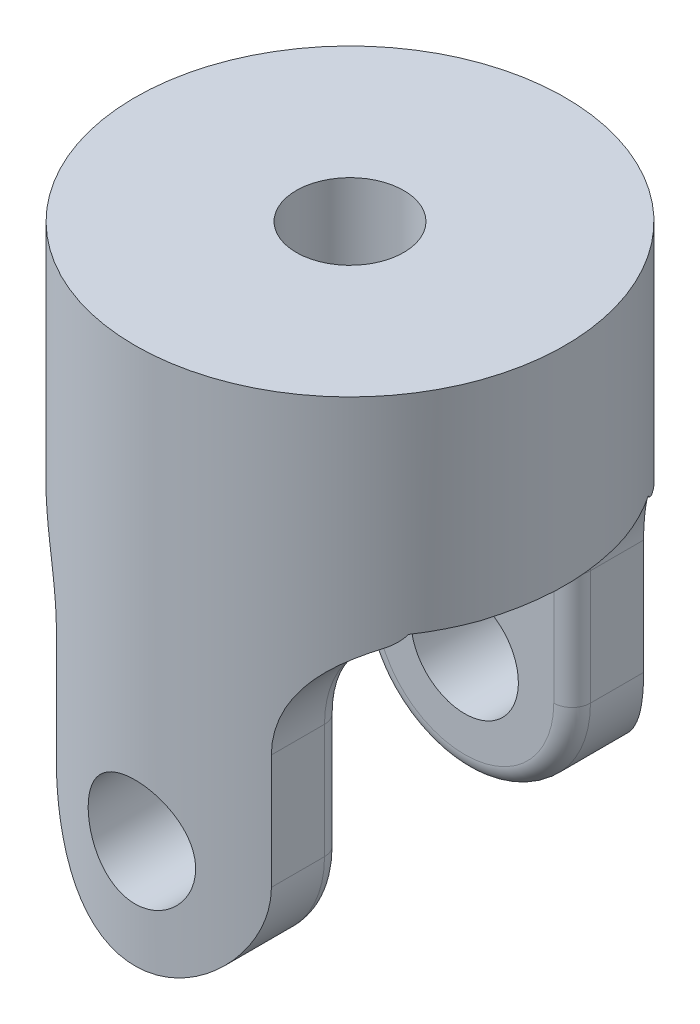
SolidWorks part; units mm, degrees
ref_plane "Front" through (0, 0, 0) normal (0, 0, 1) x (1, 0, 0)
ref_plane "Top" through (0, 0, 0) normal (0, 1, 0) x (-1, 0, 0)
ref_plane "Right" through (0, 0, 0) normal (1, 0, 0) x (0, 0, -1)
sketch "Sketch1" plane through (0, 0, 0) normal (0, 1, 0) x (-1, 0, 0)
  circle A0 centre (0, 0) radius 19.05
  dimension "D1" = 38.1
extrude "Base-Extrude" add sketch "Sketch1" along normal blind 47.625
sketch "Sketch2" plane through (0, 0, 0) normal (0, 0, 1) x (1, 0, 0)
  line L0 (0, 0) -> (0, 23.7435) construction
  line L1 (9.525, 9.525) -> (9.525, 19.685)
  line L2 (-9.525, 9.525) -> (-9.525, 19.685)
  line L3 (19.05, 29.21) -> (19.05, 0)
  line L4 (-19.05, 47.625) -> (-19.05, 0) construction
  line L5 (-19.05, 0) -> (-19.05, 29.21)
  line L6 (19.05, 0) -> (-19.05, 0) construction
  arc A0 (-9.525, 9.525) -> (9.525, 9.525) centre (0, 9.525) ccw
  arc A1 (9.525, 19.685) -> (19.05, 29.21) centre (19.05, 19.685) cw
  arc A2 (-9.525, 19.685) -> (-19.05, 29.21) centre (-19.05, 19.685) ccw
  dimension "D3" = 9.525
  dimension "D2" = 19.05
  dimension "D4" = 29.21
extrude "Cut-Extrude1" cut sketch "Sketch2" against normal through all and the other way through all flip side to cut
sketch "Sketch8" plane through (0, 0, 0) normal (1, 0, 0) x (0, 0, -1)
  line L0 (-19.05, 0) -> (19.05, 0) construction
  line L1 (-10.16, 0) -> (-10.16, 29.1452)
  line L2 (10.16, 29.1452) -> (-10.16, 29.1452)
  line L3 (10.16, 29.1452) -> (10.16, 0)
  line L4 (0, 0) -> (0, 14.3858) construction
  point P4 (0, 0)
  dimension "D1" = 29.1452
  dimension "D2" = 20.32
extrude "Cut-Extrude5" cut sketch "Sketch8" against normal through all and the other way through all flip side to cut
fillet "Fillet1" radius 1.6256 10 edges at (11.3465, 25.287, -10.16) (9.525, 14.605, -10.16) (0, 0, -10.16) (-9.525, 14.605, -10.16) (-11.3465, 25.287, -10.16) (-11.3465, 25.287, 10.16) (-9.525, 14.605, 10.16) (0, 0, 10.16) (9.525, 14.605, 10.16) (11.3465, 25.287, 10.16)
sketch "Sketch11" plane through (0, 0, 0) normal (0, 0, 1) x (1, 0, 0)
  circle A0 centre (0, 9.525) radius 4.7625
  dimension "D1" = 9.525
extrude "Cut-Extrude6" cut sketch "Sketch11" against normal through all and the other way through all
sketch "Sketch12" plane through (0, 47.625, 0) normal (0, 1, 0) x (-1, 0, 0)
  circle A0 centre (0, 0) radius 4.7625
  dimension "D1" = 9.525
extrude "Cut-Extrude7" cut sketch "Sketch12" against normal through all
ref_axis "Axis1" through (0, 97.625, 0) along (0, -1, 0)
